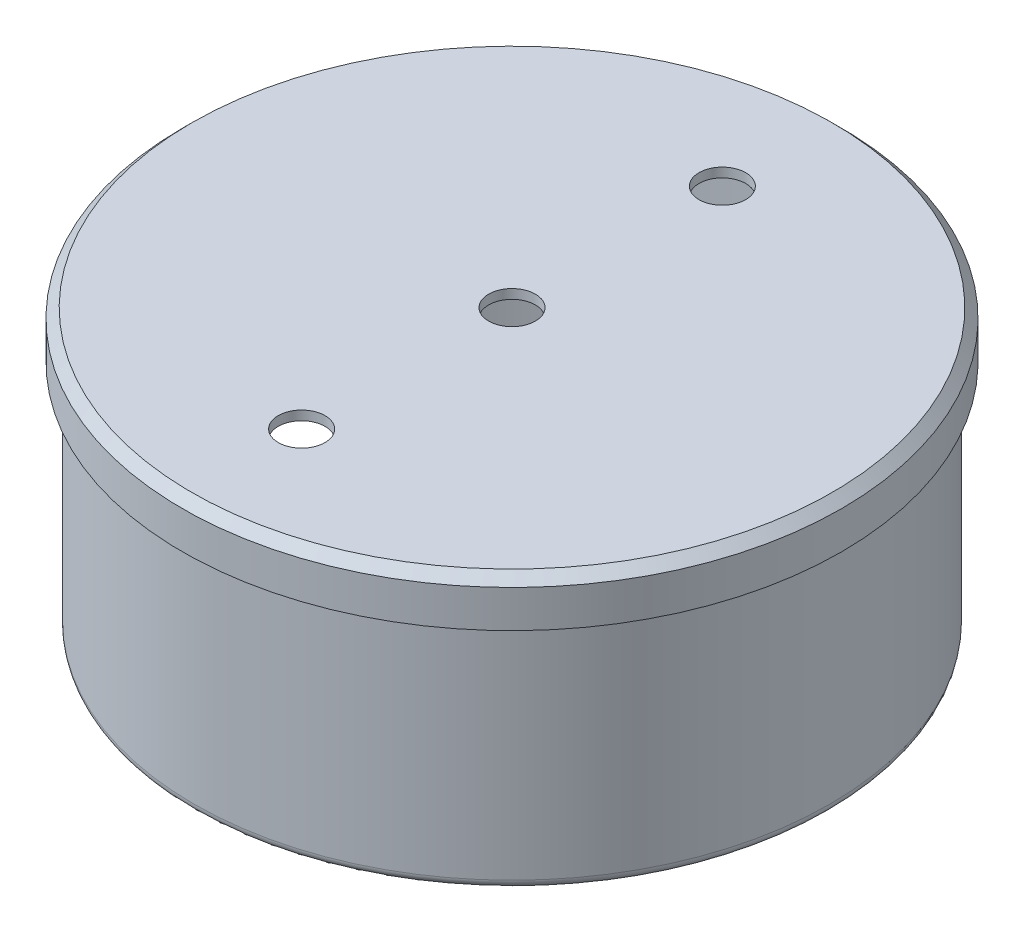
SolidWorks part; units mm, degrees
ref_plane "Piano frontale"
ref_plane "Piano superiore" through (0, 0, 0) normal (0, 1, 0) x (1, 0, 0)
ref_plane "Piano destro" through (0, 0, 0) normal (1, 0, 0) x (0, 0, -1)
sketch "Schizzo1" plane through (0, 0, 0) normal (0, 0, 1) x (1, 0, 0)
  line L3 (0, 0) -> (0, -10)
  line L4 (70.5, 0) -> (70.5, -10)
  line L5 (70.5, -10) -> (68, -10)
  line L6 (68, -10) -> (68, -58)
  line L7 (66, -60) -> (0, -60)
  line L8 (0, -60) -> (0, -10)
  line L9 (0, 0) -> (70.5, 0)
  arc A0 (68, -58) -> (66, -60) centre (66, -58) cw
  point P15 (68, -60)
  dimension "D6" = 2
  dimension "D1" = 10
  dimension "D2" = 10
  dimension "D3" = 50
  dimension "D4" = 68
  dimension "D5" = 2.5
  dimension "D8" = 70.5
revolve "Rivoluzione3" add sketch "Schizzo1" angle 360 about L8
shell "Svuota5" thickness 2 removed face at (66, -60, 0)
chamfer "Smusso1" distance 2 angle 45 1 edges at (70.5, 0, 0)
sketch "Schizzo3" plane through (0, 0, 0) normal (0, 1, 0) x (1, 0, 0)
  circle A0 centre (0, 0) radius 5
  dimension "D1" = 10
extrude "Taglio-Estrusione1" cut sketch "Schizzo3" against normal blind 10
sketch "Schizzo4" plane through (0, 0, 0) normal (0, 1, 0) x (1, 0, 0)
  line L0 (0, -51.5242) -> (0, 51.5242) construction
  circle A0 centre (0, 45) radius 5
  circle A1 centre (0, -45) radius 5
  dimension "D1" = 10
  dimension "D2" = 10
  dimension "D3" = 45
  dimension "D4" = 45
extrude "Taglio-Estrusione2" cut sketch "Schizzo4" against normal blind 10
